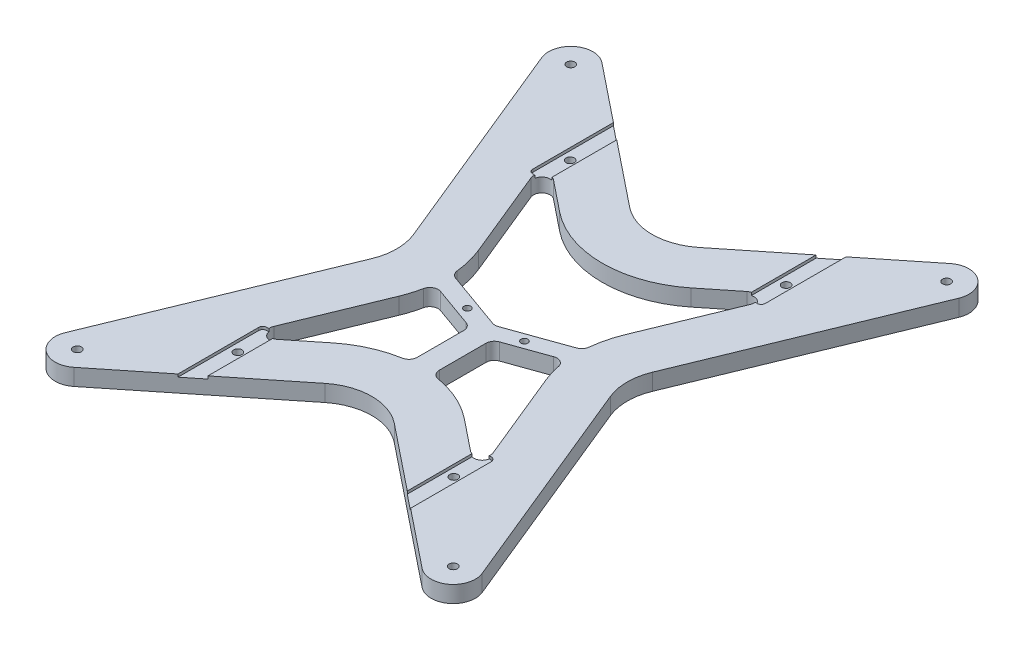
SolidWorks part; units mm, degrees
material "1060 Alloy"
ref_plane "Front Plane" through (0, 0, 0) normal (0, 0, 1) x (1, 0, 0)
ref_plane "Top Plane" through (0, 0, 0) normal (0, 1, 0) x (1, 0, 0)
ref_plane "Right Plane" through (0, 0, 0) normal (1, 0, 0) x (0, 0, -1)
sketch "Sketch1" plane through (0, 0, 0) normal (0, 1, 0) x (1, 0, 0)
  line L0 (-62.8826, 95.3407) -> (0, 45)
  line L1 (0, 45) -> (62.8826, 95.3407)
  line L2 (75.2843, 86.0607) -> (40, 0)
  line L3 (40, 0) -> (75.2843, -86.0607)
  line L4 (62.8826, -95.3407) -> (0, -45)
  line L5 (0, -45) -> (-62.8826, -95.3407)
  line L6 (-75.2843, -86.0607) -> (-40, 0)
  line L7 (-40, 0) -> (-75.2843, 86.0607)
  line L8 (-78.4889, 78.4889) -> (78.4889, -78.4889) construction
  line L9 (-42, 70) -> (-36, 70) construction
  line L10 (-42, 70) -> (-42, 50) construction
  line L11 (-42, 50) -> (-36, 50) construction
  line L12 (-36, 70) -> (-36, 50) construction
  line L13 (-42, 70) -> (-36, 50) construction
  line L14 (-42, 50) -> (-36, 70) construction
  line L15 (36, 70) -> (42, 70) construction
  line L16 (36, 70) -> (36, 50) construction
  line L17 (36, 50) -> (42, 50) construction
  line L18 (42, 70) -> (42, 50) construction
  line L19 (36, 70) -> (42, 50) construction
  line L20 (36, 50) -> (42, 70) construction
  line L21 (36, -50) -> (42, -50) construction
  line L22 (36, -50) -> (36, -70) construction
  line L23 (36, -70) -> (42, -70) construction
  line L24 (42, -50) -> (42, -70) construction
  line L25 (36, -50) -> (42, -70) construction
  line L26 (36, -70) -> (42, -50) construction
  line L27 (-42, -50) -> (-36, -50) construction
  line L28 (-42, -50) -> (-42, -70) construction
  line L29 (-42, -70) -> (-36, -70) construction
  line L30 (-36, -50) -> (-36, -70) construction
  line L31 (-42, -50) -> (-36, -70) construction
  line L32 (-42, -70) -> (-36, -50) construction
  line L33 (111, 45.9777) -> (45.9777, 111) construction
  line L34 (45.9777, 111) -> (-45.9777, 111) construction
  line L35 (-45.9777, 111) -> (-111, 45.9777) construction
  line L36 (-111, 45.9777) -> (-111, -45.9777) construction
  line L37 (-111, -45.9777) -> (-45.9777, -111) construction
  line L38 (-45.9777, -111) -> (45.9777, -111) construction
  line L39 (45.9777, -111) -> (111, -45.9777) construction
  line L40 (111, -45.9777) -> (111, 45.9777) construction
  line L41 (78.4889, 78.4889) -> (-78.4889, -78.4889) construction
  circle A0 centre (-67.8823, 89.0955) radius 1.5
  circle A1 centre (67.8823, 89.0955) radius 1.5
  circle A2 centre (-67.8823, -89.0955) radius 1.5
  circle A3 centre (67.8823, -89.0955) radius 1.5
  arc A4 (-62.8826, 95.3407) -> (-75.2843, 86.0607) centre (-67.8823, 89.0955) ccw
  arc A5 (62.8826, 95.3407) -> (75.2843, 86.0607) centre (67.8823, 89.0955) cw
  arc A6 (-75.2843, -86.0607) -> (-62.8826, -95.3407) centre (-67.8823, -89.0955) ccw
  arc A7 (75.2843, -86.0607) -> (62.8826, -95.3407) centre (67.8823, -89.0955) cw
  circle A8 centre (0, 0) radius 111 construction
  circle A9 centre (-39, 60) radius 1.5
  circle A10 centre (39, 60) radius 1.5
  circle A11 centre (39, -60) radius 1.5
  circle A12 centre (-39, -60) radius 1.5
  ellipse E0 centre (0, 0) end of major axis (0, 45) minor radius 40 construction
  dimension "D5" = 3
  dimension "D6" = 45
  dimension "D7" = 8
  dimension "D12" = 3
  dimension "D3" = 15
  dimension "D4" = 15
  dimension "D8" = 120
  dimension "D9" = 78
  dimension "D10" = 0
  dimension "D11" = 60
  dimension "D13" = 40
  dimension "D14" = 39
  dimension "D15" = 20
  dimension "D16" = 6
  dimension "D17" = 111
  dimension "D18" = 15
extrude "Boss-Extrude1" add sketch "Sketch1" along normal blind 6
fillet "Fillet1" radius 20 4 edges at (0, 3, -45) (-40, 3, 0) (0, 3, 45) (40, 3, 0)
sketch "Sketch2" plane through (0, 6, 0) normal (0, 1, 0) x (1, 0, 0)
  line L44 (-43.976, 57.1476) -> (-26.456, 14.4152)
  line L45 (-26.456, -14.4152) -> (-43.976, -57.1476)
  line L46 (-43.976, -57.1476) -> (-23.7484, -40.9543)
  line L47 (23.7484, -40.9543) -> (43.976, -57.1476)
  line L48 (43.976, -57.1476) -> (26.456, -14.4152)
  line L49 (26.456, 14.4152) -> (43.976, 57.1476)
  line L50 (43.976, 57.1476) -> (23.7484, 40.9543)
  line L51 (-23.7484, 40.9543) -> (-43.976, 57.1476)
  line L52 (-43.976, 57.1476) -> (-26.456, 14.4152)
  line L53 (-26.456, -14.4152) -> (-43.976, -57.1476)
  line L54 (-43.976, -57.1476) -> (-23.7484, -40.9543)
  line L55 (23.7484, -40.9543) -> (43.976, -57.1476)
  line L56 (43.976, -57.1476) -> (26.456, -14.4152)
  line L57 (26.456, 14.4152) -> (43.976, 57.1476)
  line L58 (43.976, 57.1476) -> (23.7484, 40.9543)
  line L59 (-23.7484, 40.9543) -> (-43.976, 57.1476)
  arc A40 (-26.456, -14.4152) -> (-26.456, 14.4152) centre (-61.6157, 0) ccw
  arc A41 (23.7484, -40.9543) -> (-23.7484, -40.9543) centre (0, -70.6194) ccw
  arc A42 (26.456, 14.4152) -> (26.456, -14.4152) centre (61.6157, 0) ccw
  arc A43 (-23.7484, 40.9543) -> (23.7484, 40.9543) centre (0, 70.6194) ccw
  arc A44 (-26.456, -14.4152) -> (-26.456, 14.4152) centre (-61.6157, 0) ccw
  arc A45 (23.7484, -40.9543) -> (-23.7484, -40.9543) centre (0, -70.6194) ccw
  arc A46 (26.456, 14.4152) -> (26.456, -14.4152) centre (61.6157, 0) ccw
  arc A47 (-23.7484, 40.9543) -> (23.7484, 40.9543) centre (0, 70.6194) ccw
  dimension "D1" = 18
extrude "Cut-Extrude1" cut sketch "Sketch2" against normal up to next
sketch "Sketch5" plane through (0, 6, 0) normal (0, 1, 0) x (1, 0, 0)
  line L0 (-25.6062, 2.8251) -> (0, -6.3247)
  line L1 (-12.94, -8.43) -> (12.94, -8.43) construction
  line L2 (-12.94, -8.43) -> (-12.94, 8.43) construction
  line L3 (-12.94, 8.43) -> (12.94, 8.43) construction
  line L4 (12.94, -8.43) -> (12.94, 8.43) construction
  line L5 (-12.94, -8.43) -> (12.94, 8.43) construction
  line L6 (-12.94, 8.43) -> (12.94, -8.43) construction
  line L8 (0, -6.3247) -> (25.6062, 2.8251)
  line L10 (25.6062, 2.8251) -> (27.6251, -2.8251)
  line L11 (27.6251, -2.8251) -> (4, -11.2669)
  line L12 (4, -11.2669) -> (4, -32.8305)
  line L13 (-4, -32.8305) -> (-4, -11.2669)
  line L14 (-4, -11.2669) -> (-27.6251, -2.8251)
  line L15 (-27.6251, -2.8251) -> (-25.6062, 2.8251)
  line L17 (26.6157, 0) -> (-26.6157, 0) construction
  circle A0 centre (-10.3, -5.83) radius 1.25
  circle A1 centre (10.3, -5.83) radius 1.25
  arc A2 (23.7484, -40.9543) -> (-23.7484, -40.9543) centre (0, -70.6194) ccw construction
  arc A3 (4, -32.8305) -> (-4, -32.8305) centre (0, -70.6194) ccw
  arc A4 (-26.456, -14.4152) -> (-26.456, 14.4152) centre (-61.6157, 0) ccw construction
  arc A5 (26.456, 14.4152) -> (26.456, -14.4152) centre (61.6157, 0) ccw construction
  circle A6 centre (26.6157, 0) radius 3 construction
  circle A7 centre (-26.6157, 0) radius 3 construction
  point P0 (0, 0)
  dimension "D3" = 2.5
  dimension "D10" = 6
  dimension "D1" = 16.86
  dimension "D2" = 25.88
  dimension "D4" = 20.6
  dimension "D5" = 2.64
  dimension "D6" = 2.6
  dimension "D7" = 6
  dimension "D8" = 3
  dimension "D9" = 8
extrude "Boss-Extrude2" add sketch "Sketch5" against normal up to surface (6 mm away) up to face at (0, 0, 0)
fillet "Fillet2" radius 3 13 edges at (43.976, 3, 57.1476) (-43.976, 3, 57.1476) (43.976, 3, -57.1476) (-43.976, 3, -57.1476) (0, 3, 6.3247) (4, 3, 11.2669) (4, 3, 32.8305) (-4, 3, 32.8305) (-4, 3, 11.2669) (23.6757, 3, -2.1352) (-23.6757, 3, -2.1352) (23.8458, 3, 4.1755) (-23.8458, 3, 4.1755)
sketch "Sketch6" plane through (0, 6, 0) normal (0, 1, 0) x (1, 0, 0)
  line L0 (-12.4991, 55.0062) -> (-62.8826, 95.3407) construction
  line L1 (-42, -48) -> (-36, -48)
  line L2 (-42, -48) -> (-42, -78.6231)
  line L3 (-42, -78.6231) -> (-36, -78.6231)
  line L4 (-36, -48) -> (-36, -78.6231)
  line L5 (36, -48) -> (42, -48)
  line L6 (36, -48) -> (36, -78.6231)
  line L7 (36, -78.6231) -> (42, -78.6231)
  line L8 (42, -48) -> (42, -78.6231)
  line L9 (36, 48) -> (42, 48)
  line L10 (36, 48) -> (36, 78.6231)
  line L11 (36, 78.6231) -> (42, 78.6231)
  line L12 (42, 48) -> (42, 78.6231)
  line L13 (-42, 48) -> (-36, 48)
  line L14 (-42, 48) -> (-42, 78.6231)
  line L15 (-42, 78.6231) -> (-36, 78.6231)
  line L16 (-36, 48) -> (-36, 78.6231)
  line L17 (62.8826, 95.3407) -> (12.4991, 55.0062) construction
  line L18 (12.4991, -55.0062) -> (62.8826, -95.3407) construction
  line L19 (-62.8826, -95.3407) -> (-12.4991, -55.0062) construction
  circle A0 centre (-39, -60) radius 1.5 construction
  circle A1 centre (39, -60) radius 1.5 construction
  circle A2 centre (-39, 60) radius 1.5 construction
  dimension "D2" = 3
  dimension "D3" = 3
  dimension "D5" = 12
  dimension "D1" = 6
  dimension "D4" = 12
extrude "Cut-Extrude2" cut sketch "Sketch6" against normal blind 1
fillet "Fillet3" radius 1.5 4 edges at (-42, 5.5, -48) (42, 5.5, -48) (42, 5.5, 48) (-42, 5.5, 48)
equation "\"D14@Sketch1\"=\"D9@Sketch1\"/2"
